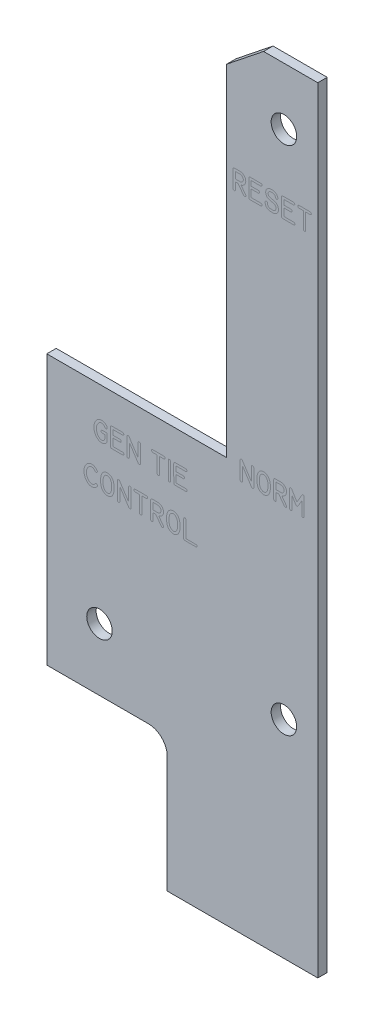
SolidWorks part; units mm, degrees
ref_plane "Front Plane" through (0, 0, 0) normal (0, 0, 1) x (1, 0, 0)
ref_plane "Top Plane" through (0, 0, 0) normal (0, 1, 0) x (1, 0, 0)
ref_plane "Right Plane" through (0, 0, 0) normal (1, 0, 0) x (0, 0, -1)
sketch "Sketch1" plane through (0, 0, 0) normal (0, 0, 1) x (1, 0, 0)
  line L3 (-15.3921, 125.8202) -> (-15.3921, 68.3432)
  line L4 (-15.3921, 68.3432) -> (-45.72, 68.3432)
  line L6 (0, 130.81) -> (0, 0)
  line L7 (-15.3921, 125.8202) -> (-9.144, 130.81)
  line L8 (-9.144, 130.81) -> (0, 130.81)
  line L19 (-25.4, 0) -> (0, 0)
  line L20 (-25.4, 19.685) -> (-25.4, 0)
  line L21 (-45.72, 22.86) -> (-28.575, 22.86)
  line L22 (-45.72, 68.3432) -> (-45.72, 22.86)
  arc A1 (-25.4, 19.685) -> (-28.575, 22.86) centre (-28.575, 19.685) ccw
extrude "Boss-Extrude1" add sketch "Sketch1" along normal blind 1.5875
sketch "Sketch2" plane through (0, 0, 1.5875) normal (0, 0, 1) x (1, 0, 0)
  line L0 (-15.24, 107.9999) -> (0, 107.9999) construction
  line L3 (-15.24, 66.04) -> (0, 66.04) construction
  line L4 (-15.24, 66.04) -> (-15.24, 50.8) construction
  line L6 (-15.24, 59.9598) -> (-44.45, 59.9598) construction
  line L8 (-15.24, 52.7037) -> (-44.45, 52.7037) construction
  text T0 "RESET"
  text T1 "NORM"
  text T2 "GEN TIE"
  text T3 "CONTROL"
wrap "Wrap1" sketch "Sketch2" wrap type scribe source sketch "Sketch2" face at (-21.0086, 59.0189, 1.5875)
sketch "Sketch4" plane through (0, 0, 0) normal (0, 0, -1) x (-1, 0, 0)
  circle A0 centre (5.715, 121.158) radius 2.1527
  circle A2 centre (5.715, 34.925) radius 2.1526
  circle A3 centre (36.83, 33.3375) radius 2.1527
  dimension "D1" = 4.3053
extrude "Cut-Extrude1" cut sketch "Sketch4" against normal through all
